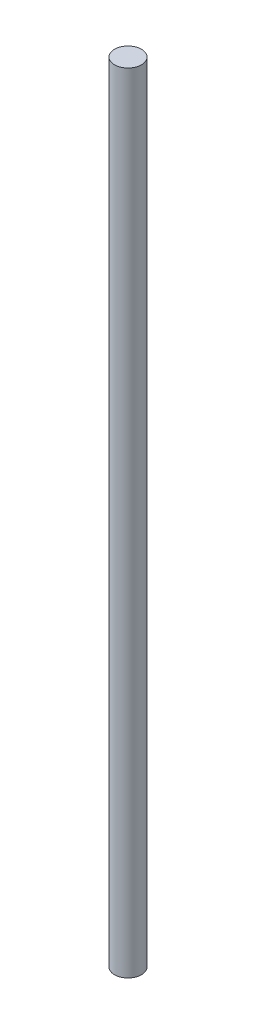
SolidWorks part; units mm, degrees
ref_plane "Front Plane" through (0, 0, 0) normal (0, 0, 1) x (1, 0, 0)
ref_plane "Top Plane" through (0, 0, 0) normal (0, 1, 0) x (1, 0, 0)
ref_plane "Right Plane" through (0, 0, 0) normal (1, 0, 0) x (0, 0, -1)
sketch "Sketch1" plane through (0, 0, 0) normal (0, 1, 0) x (1, 0, 0)
  circle A0 centre (0, 0) radius 0.855
  dimension "D1" = 1.71
extrude "Boss-Extrude1" add sketch "Sketch1" along normal mid plane 50
